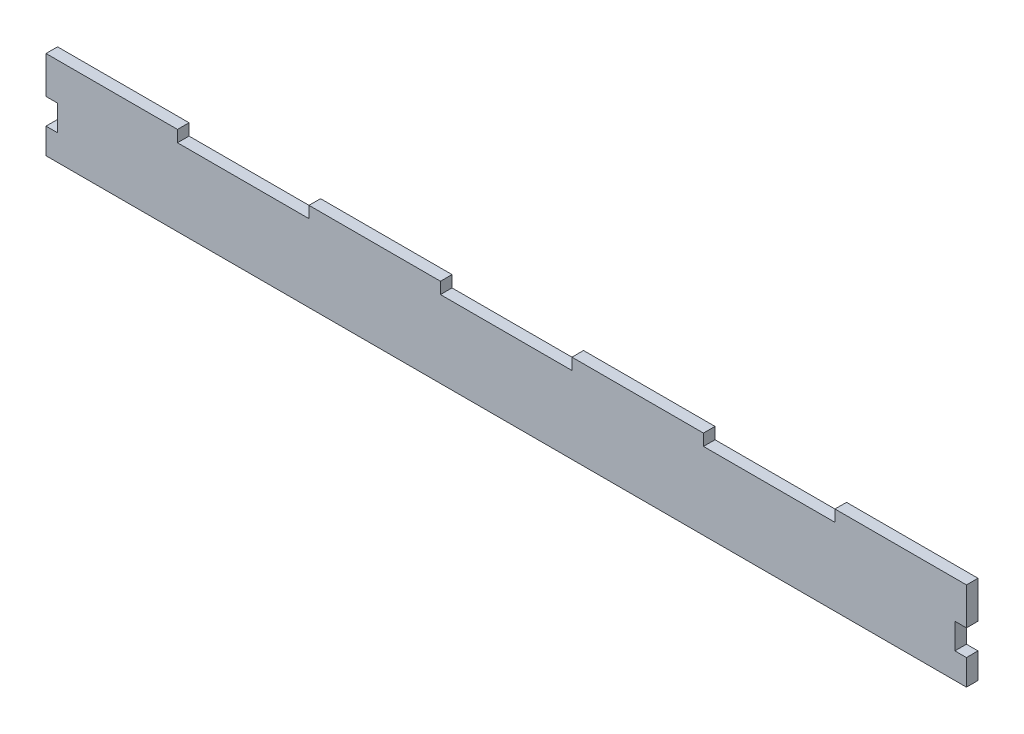
SolidWorks part; units mm, degrees
ref_plane "Front Plane" through (0, 0, 0) normal (0, 0, 1) x (1, 0, 0)
ref_plane "Top Plane" through (0, 0, 0) normal (0, 1, 0) x (1, 0, 0)
ref_plane "Right Plane" through (0, 0, 0) normal (1, 0, 0) x (0, 0, -1)
sketch "Sketch1" plane through (0, 0, 0) normal (0, 1, 0) x (1, 0, 0)
  line L1 (-233, -63.25) -> (233, -63.25)
  line L2 (-233, -63.25) -> (-233, 63.25)
  line L3 (-233, 63.25) -> (233, 63.25)
  line L4 (233, -63.25) -> (233, 63.25)
  line L5 (-233, -63.25) -> (233, 63.25) construction
  line L6 (-233, 63.25) -> (233, -63.25) construction
  point P0 (0, 0)
  dimension "D1" = 126.5
  dimension "D2" = 466
extrude "Boss-Extrude1" add sketch "Sketch1" along normal blind 6
sketch "Sketch2" plane through (0, 6, 0) normal (0, 1, 0) x (1, 0, 0)
  line L0 (239, -69.25) -> (239, 69.25)
  line L3 (-239, -69.25) -> (239, -69.25)
  line L4 (233, -63.25) -> (233, 63.25)
  line L5 (233, 63.25) -> (-233, 63.25)
  line L6 (-233, 63.25) -> (-233, -63.25)
  line L7 (-233, -63.25) -> (233, -63.25)
  line L8 (233, -63.25) -> (233, 63.25)
  line L9 (233, 63.25) -> (-233, 63.25)
  line L10 (-233, 63.25) -> (-233, -63.25)
  line L11 (-233, -63.25) -> (233, -63.25)
  line L12 (257, -87.25) -> (257, 87.25)
  line L13 (257, 87.25) -> (-257, 87.25)
  line L14 (-257, 87.25) -> (-257, -87.25)
  line L15 (-257, -87.25) -> (257, -87.25)
  line L16 (263, -93.25) -> (263, 93.25)
  line L19 (-263, -93.25) -> (263, -93.25)
  line L20 (239, 69.25) -> (-239, 69.25) construction
  line L21 (-239, 69.25) -> (-239, -69.25) construction
  line L22 (-239, -69.25) -> (-239, -63.25)
  line L27 (170.7143, 69.25) -> (102.4286, 69.25)
  line L28 (170.7143, 69.25) -> (170.7143, 63.25)
  line L29 (170.7143, 63.25) -> (102.4286, 63.25)
  line L30 (102.4286, 69.25) -> (102.4286, 63.25)
  line L31 (102.4286, 69.25) -> (34.1429, 69.25)
  line L32 (102.4286, 69.25) -> (102.4286, 63.25)
  line L33 (102.4286, 63.25) -> (34.1429, 63.25)
  line L34 (34.1429, 69.25) -> (34.1429, 63.25)
  line L35 (34.1429, 69.25) -> (-34.1429, 69.25)
  line L36 (34.1429, 69.25) -> (34.1429, 63.25)
  line L37 (34.1429, 63.25) -> (-34.1429, 63.25)
  line L38 (-34.1429, 69.25) -> (-34.1429, 63.25)
  line L39 (-34.1429, 69.25) -> (-102.4286, 69.25)
  line L40 (-34.1429, 69.25) -> (-34.1429, 63.25)
  line L41 (-34.1429, 63.25) -> (-102.4286, 63.25)
  line L42 (-102.4286, 69.25) -> (-102.4286, 63.25)
  line L43 (-102.4286, 69.25) -> (-170.7143, 69.25)
  line L44 (-102.4286, 69.25) -> (-102.4286, 63.25)
  line L45 (-102.4286, 63.25) -> (-170.7143, 63.25)
  line L46 (-170.7143, 69.25) -> (-170.7143, 63.25)
  line L47 (-170.7143, 69.25) -> (-239, 69.25)
  line L48 (-170.7143, 69.25) -> (-170.7143, 63.25)
  line L49 (-170.7143, 63.25) -> (-239, 63.25)
  line L50 (-239, 69.25) -> (-239, 63.25)
  line L51 (-239, 63.25) -> (-233, 63.25)
  line L52 (-239, 63.25) -> (-239, 37.95)
  line L53 (-239, 37.95) -> (-233, 37.95)
  line L54 (-233, 63.25) -> (-233, 37.95)
  line L55 (-233, 37.95) -> (-239, 37.95)
  line L56 (-233, 37.95) -> (-233, 12.65)
  line L57 (-233, 12.65) -> (-239, 12.65)
  line L58 (-239, 37.95) -> (-239, 12.65)
  line L59 (-239, 12.65) -> (-233, 12.65)
  line L60 (-239, 12.65) -> (-239, -12.65)
  line L61 (-239, -12.65) -> (-233, -12.65)
  line L62 (-233, 12.65) -> (-233, -12.65)
  line L63 (-233, -12.65) -> (-239, -12.65)
  line L64 (-233, -12.65) -> (-233, -37.95)
  line L65 (-233, -37.95) -> (-239, -37.95)
  line L66 (-239, -12.65) -> (-239, -37.95)
  line L67 (-239, -37.95) -> (-233, -37.95)
  line L68 (-239, -37.95) -> (-239, -63.25)
  line L69 (-239, -63.25) -> (-233, -63.25)
  line L70 (-233, -37.95) -> (-233, -63.25)
  line L71 (170.7143, 63.25) -> (239, 63.25)
  line L72 (170.7143, 63.25) -> (170.7143, 69.25)
  line L73 (170.7143, 69.25) -> (239, 69.25)
  line L74 (239, 63.25) -> (239, 69.25)
  line L75 (-263, 93.25) -> (-257, 93.25)
  line L76 (-263, 93.25) -> (-263, 55.95)
  line L77 (-263, 55.95) -> (-257, 55.95)
  line L78 (-257, 93.25) -> (-257, 55.95)
  line L79 (-263, 93.25) -> (-263, -93.25) construction
  line L80 (-257, 55.95) -> (-263, 55.95)
  line L81 (-257, 55.95) -> (-257, 18.65)
  line L82 (-257, 18.65) -> (-263, 18.65)
  line L83 (-263, 55.95) -> (-263, 18.65)
  line L84 (-263, 18.65) -> (-257, 18.65)
  line L85 (-263, 18.65) -> (-263, -18.65)
  line L86 (-263, -18.65) -> (-257, -18.65)
  line L87 (-257, 18.65) -> (-257, -18.65)
  line L88 (-257, -18.65) -> (-263, -18.65)
  line L89 (-257, -18.65) -> (-257, -55.95)
  line L90 (-257, -55.95) -> (-263, -55.95)
  line L91 (-263, -18.65) -> (-263, -55.95)
  line L92 (-263, -55.95) -> (-257, -55.95)
  line L93 (-263, -55.95) -> (-263, -93.25)
  line L94 (-263, -93.25) -> (-257, -93.25)
  line L95 (-257, -55.95) -> (-257, -93.25)
  line L96 (257, 87.25) -> (183.5714, 87.25)
  line L97 (257, 87.25) -> (257, 93.25)
  line L98 (257, 93.25) -> (183.5714, 93.25)
  line L99 (183.5714, 87.25) -> (183.5714, 93.25)
  line L100 (183.5714, 93.25) -> (110.1429, 93.25)
  line L101 (183.5714, 93.25) -> (183.5714, 87.25)
  line L102 (183.5714, 87.25) -> (110.1429, 87.25)
  line L103 (110.1429, 93.25) -> (110.1429, 87.25)
  line L104 (110.1429, 87.25) -> (36.7143, 87.25)
  line L105 (110.1429, 87.25) -> (110.1429, 93.25)
  line L106 (110.1429, 93.25) -> (36.7143, 93.25)
  line L107 (36.7143, 87.25) -> (36.7143, 93.25)
  line L108 (36.7143, 93.25) -> (-36.7143, 93.25)
  line L109 (36.7143, 93.25) -> (36.7143, 87.25)
  line L110 (36.7143, 87.25) -> (-36.7143, 87.25)
  line L111 (-36.7143, 93.25) -> (-36.7143, 87.25)
  line L112 (-36.7143, 87.25) -> (-110.1429, 87.25)
  line L113 (-36.7143, 87.25) -> (-36.7143, 93.25)
  line L114 (-36.7143, 93.25) -> (-110.1429, 93.25)
  line L115 (-110.1429, 87.25) -> (-110.1429, 93.25)
  line L116 (-110.1429, 93.25) -> (-183.5714, 93.25)
  line L117 (-110.1429, 93.25) -> (-110.1429, 87.25)
  line L118 (-110.1429, 87.25) -> (-183.5714, 87.25)
  line L119 (-183.5714, 93.25) -> (-183.5714, 87.25)
  line L120 (-183.5714, 87.25) -> (-257, 87.25)
  line L121 (-183.5714, 87.25) -> (-183.5714, 93.25)
  line L122 (-183.5714, 93.25) -> (-257, 93.25)
  line L123 (-257, 87.25) -> (-257, 93.25)
  line L124 (263, 93.25) -> (-263, 93.25) construction
  line L125 (263, 93.25) -> (257, 93.25)
  line M93 (233, 63.25) -> (-233, 63.25)
  dimension "D1" = 0
  dimension "D2" = 6
  dimension "D3" = 18
  dimension "D4" = 6
extrude "Boss-Extrude2" add sketch "Sketch2" against normal blind 40 contours L47 L50 L49 L46 M93 | L43 L46 L9 L42 | L39 L42 L38 M93 | L35 L38 L9 L34 | L31 L34 L30 M93 | L27 L30 L9 L28 | L73 L28 L71 L0 M93 region at (204.8571, 6, -66.25) region at (136.5714, 6, -66.25) region at (68.2857, 6, -66.25) region at (0, 6, -66.25) region at (-68.2857, 6, -66.25) region at (-136.5714, 6, -66.25) region at (-204.8571, 6, -66.25)
extrude "Cut-Extrude1" cut sketch "Sketch1<2>" against normal through all both and the other way through all
sketch "Sketch1<2>" plane through (0, 0, 0) normal (0, 1, 0) x (1, 0, 0) same geometry as "Sketch1"
extrude "Boss-Extrude3" add sketch "Sketch2<4>" along normal blind 6 contours L47 L50 L49 L46 M93 | L39 L42 L38 M93 | L31 L34 L30 M93 | L73 L28 L71 L0 M93 region at (204.8571, 6, -66.25) region at (68.2857, 6, -66.25) region at (-68.2857, 6, -66.25) region at (-204.8571, 6, -66.25)
sketch "Sketch2<4>" plane through (0, 6, 0) normal (0, 1, 0) x (1, 0, 0) same geometry as "Sketch2"
sketch "Sketch3" plane through (0, 0, -63.25) normal (0, 0, 1) x (1, 0, 0)
  line L0 (-239, -34) -> (-239, 12) construction
  line L1 (-239, -34) -> (-233, -34)
  line L2 (-239, -34) -> (-239, -20.6667)
  line L3 (-239, -20.6667) -> (-233, -20.6667)
  line L4 (-233, -34) -> (-233, -20.6667)
  line L5 (-233, -20.6667) -> (-239, -20.6667)
  line L6 (-233, -20.6667) -> (-233, -7.3333)
  line L7 (-233, -7.3333) -> (-239, -7.3333)
  line L8 (-239, -20.6667) -> (-239, -7.3333)
  line L10 (-239, -7.3333) -> (-233, -7.3333)
  line L11 (-239, -7.3333) -> (-239, 6)
  line L12 (-239, 6) -> (-233, 6)
  line L13 (-233, -7.3333) -> (-233, 6)
  line L14 (-233, 6) -> (-239, 6) construction
  line M8 (-239, 12) -> (-239, -34)
  dimension "D1" = 6
extrude "Cut-Extrude2" cut sketch "Sketch3" against normal blind 6 contours L6 L7 L3 M8 region at (-236, -14, -63.25)
mirror "Mirror1" about plane through (0, 0, 0) normal (1, 0, 0) of "Cut-Extrude2"
